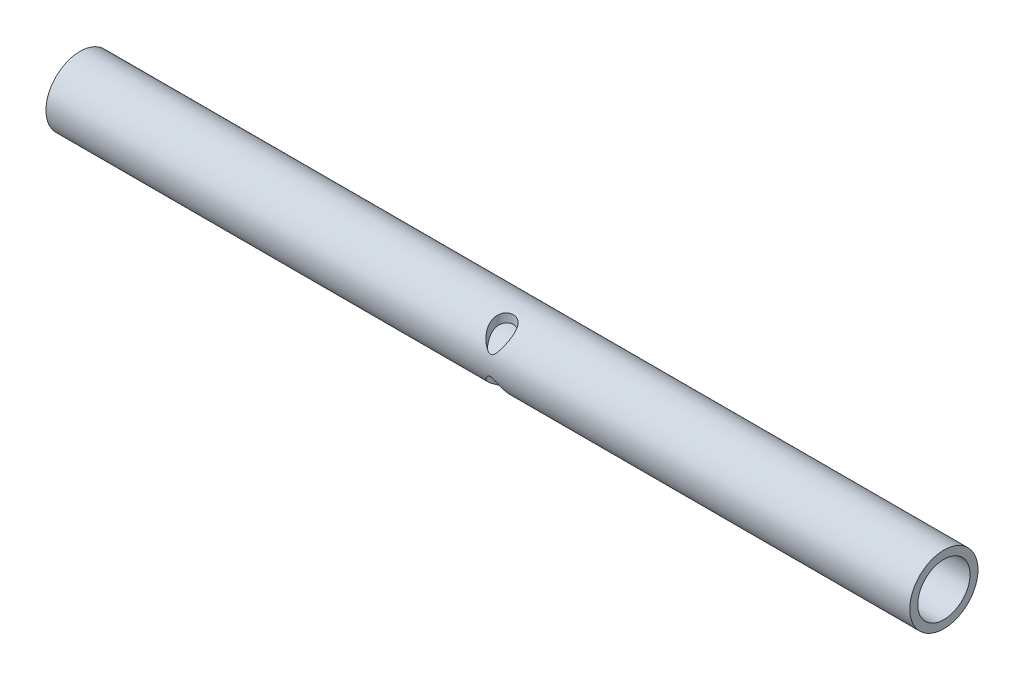
SolidWorks part; units mm, degrees
material "Hexcel AS4C (3000 Filaments)"
ref_plane "Front Plane" through (0, 0, 0) normal (0, 0, 1) x (1, 0, 0)
ref_plane "Top Plane" through (0, 0, 0) normal (0, 1, 0) x (1, 0, 0)
ref_plane "Right Plane" through (0, 0, 0) normal (1, 0, 0) x (0, 0, -1)
sketch "Sketch1" plane through (0, 0, 0) normal (1, 0, 0) x (0, 0, -1)
  circle A0 centre (0, 0) radius 3.048
  circle A1 centre (0, 0) radius 2.3368
  dimension "D1" = 6.096
  dimension "D2" = 4.6736
extrude "Boss-Extrude1" add sketch "Sketch1" along normal blind 38.608 and the other way blind 38.608
sketch "Sketch4" plane through (1.016, 0, 1.9075) normal (0, -1, 0) x (0.9781, 0, -0.2083)
  circle A0 centre (0, 0) radius 1.016
extrude "Cut-Extrude2" cut sketch "Sketch4" against normal through all and the other way through all
